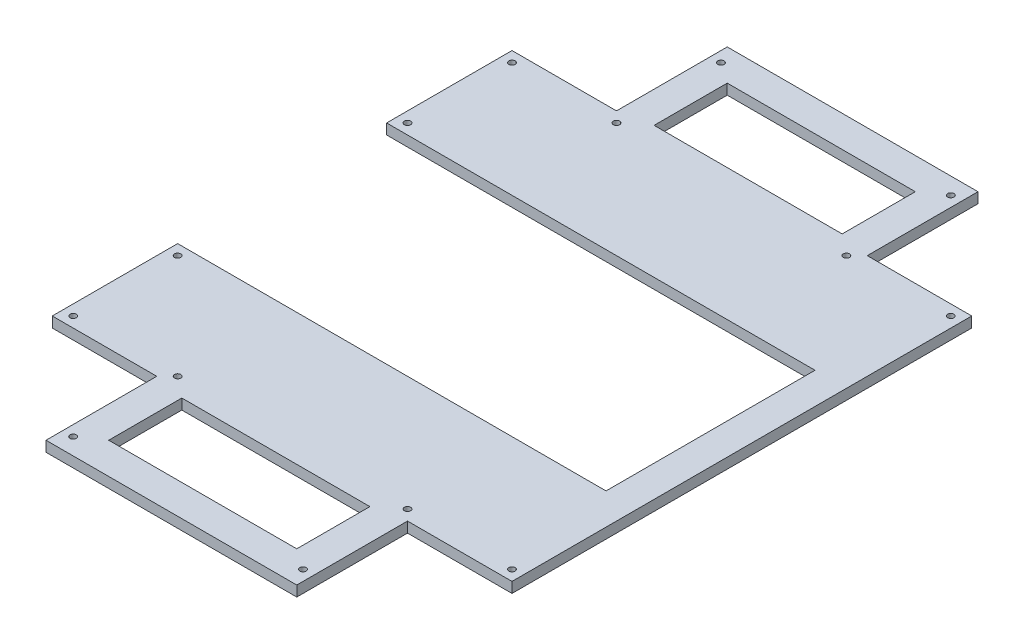
SolidWorks part; units mm, degrees
ref_plane "Plan de face" through (0, 0, 0) normal (0, 0, 1) x (1, 0, 0)
ref_plane "Plan de dessus" through (0, 0, 0) normal (0, 1, 0) x (1, 0, 0)
ref_plane "Plan de droite" through (0, 0, 0) normal (1, 0, 0) x (0, 0, -1)
sketch "Esquisse1" plane through (0, 0, 0) normal (0, 1, 0) x (1, 0, 0)
  line L0 (-60, 110) -> (-60, 163)
  line L1 (110, -110) -> (60, -110)
  line L2 (110, -110) -> (110, 110)
  line L3 (110, 110) -> (60, 110)
  line L4 (-110, -110) -> (-110, -50)
  line L5 (110, -110) -> (-110, 110) construction
  line L6 (110, 110) -> (-110, -110) construction
  line L7 (-60, 163) -> (60, 163)
  line L8 (60, 163) -> (60, 110)
  line L9 (0, 163) -> (0, -89.8749) construction
  line L10 (-108.9276, 0) -> (110, 0) construction
  line L11 (-105, -105) -> (-105, -50) construction
  line L12 (-55, -105) -> (-55, -163) construction
  line L13 (-60, 110) -> (-110, 110)
  line L14 (60, -163) -> (60, -110)
  line L15 (-60, -163) -> (60, -163)
  line L16 (-60, -110) -> (-60, -163)
  line L17 (-60, -110) -> (-110, -110)
  line L18 (45, -148) -> (-45, -148)
  line L19 (45, 113) -> (-45, 113)
  line L20 (45, 113) -> (45, 148)
  line L21 (45, 148) -> (-45, 148)
  line L22 (-45, 113) -> (-45, 148)
  line L23 (45, 113) -> (-45, 148) construction
  line L24 (45, 148) -> (-45, 113) construction
  line L25 (-45, -113) -> (-45, -148)
  line L26 (45, -113) -> (-45, -113)
  line L27 (45, -113) -> (45, -148)
  line L28 (-110, 50) -> (-110, 110)
  line L29 (95, -50) -> (-110, -50)
  line L30 (95, -50) -> (95, 50)
  line L31 (95, 50) -> (-110, 50)
  line L33 (-105, -105) -> (105, -105) construction
  line L34 (105, -105) -> (105, 0) construction
  line L36 (-55, 105) -> (-55, 155) construction
  line L37 (-55, 155) -> (55, 155) construction
  line L38 (55, 155) -> (55, 105) construction
  line L39 (55, 105) -> (55, 155) construction
  circle A0 centre (-105, -105) radius 1.5
  circle A1 centre (-105, -55) radius 1.5
  circle A2 centre (-55, -105) radius 1.5
  circle A5 centre (-5, -105) radius 1.5 [skipped]
  circle A6 centre (45, -105) radius 1.5 [skipped]
  circle A7 centre (-55, -155) radius 1.5
  circle A9 centre (-55, 105) radius 1.5
  circle A10 centre (-105, 105) radius 1.5
  circle A11 centre (-105, 55) radius 1.5
  circle A12 centre (55, -155) radius 1.5
  circle A13 centre (55, -105) radius 1.5
  circle A14 centre (105, -105) radius 1.5
  circle A15 centre (105, 105) radius 1.5
  circle A16 centre (55, 105) radius 1.5
  circle A18 centre (-55, 155) radius 1.5
  circle A19 centre (55, 155) radius 1.5
  point P0 (0, 0)
  point P23 (0, 130.5)
  point P28 (-45, 130.5)
  point P33 (0.5362, 0)
  dimension "D4" = 3
  dimension "D6" = 53
  dimension "D14" = 5
  dimension "D16" = 8
  dimension "D1" = 220
  dimension "D2" = 50
  dimension "D3" = 50
  dimension "D5" = 5
  dimension "D7" = 2
  dimension "D8" = 15
  dimension "D9" = 15
  dimension "D10" = 15
  dimension "D11" = 60
  dimension "D13" = 2
  dimension "D12" = 60
  dimension "D18" = 120
  dimension "D20" = 50
  dimension "D21" = 3
  dimension "D15" = 4
  dimension "D17" = 2
  dimension "D19" = 2
extrude "Boss.-Extru.1" add sketch "Esquisse1" along normal blind 5
